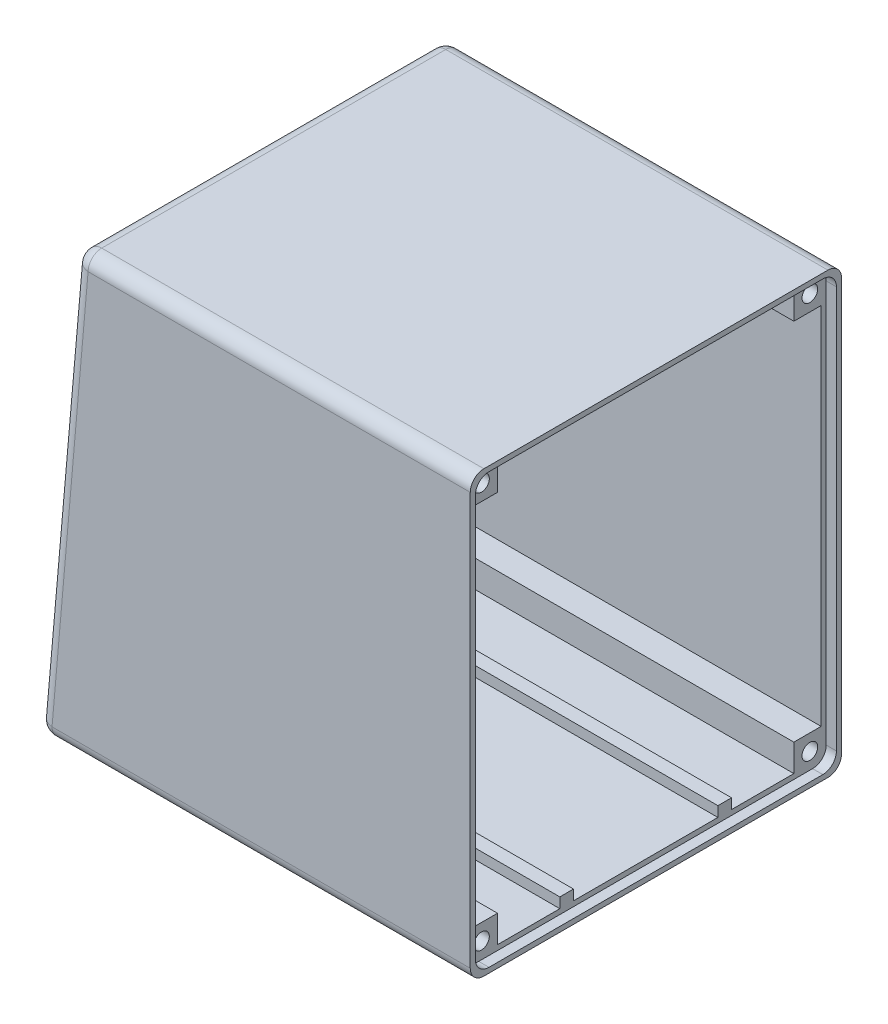
SolidWorks part; units mm, degrees
material "POM 乙缩醛共聚物"
ref_plane "前视基准面" through (0, 0, 0) normal (0, 0, 1) x (1, 0, 0)
ref_plane "上视基准面" through (0, 0, 0) normal (0, 1, 0) x (1, 0, 0)
ref_plane "右视基准面" through (0, 0, 0) normal (1, 0, 0) x (0, 0, -1)
sketch "草图1" plane through (0, 0, 0) normal (0, 0, 1) x (1, 0, 0)
  line L0 (0, 0) -> (62, 0)
  line L1 (0, 0) -> (5.5118, 63)
  line L2 (5.5118, 63) -> (62, 63)
  line L3 (62, 0) -> (62, 63)
  dimension "D1" = 85
  dimension "D2" = 62
  dimension "D3" = 63
extrude "拉伸-薄壁1" add sketch "草图1" along normal mid plane 53 thin thin type mid plane wall 1.5
sketch "草图2" plane through (0, 0, -26.5) normal (0, 0, -1) x (-1, 0, 0)
  line L4 (0.8185, -0.75) -> (-4.8245, 63.75)
  line L5 (-4.8245, 63.75) -> (-62.75, 63.75)
  line L6 (-62.75, 63.75) -> (-62.75, -0.75)
  line L7 (-62.75, -0.75) -> (0.8185, -0.75)
  line L8 (0.8185, -0.75) -> (-4.8245, 63.75)
  line L9 (-4.8245, 63.75) -> (-62.75, 63.75)
  line L10 (-62.75, 63.75) -> (-62.75, -0.75)
  line L11 (-62.75, -0.75) -> (0.8185, -0.75)
  dimension "D1" = 0
extrude "凸台-拉伸1" add sketch "草图2" along normal mid plane 1.5
sketch "草图3" plane through (0, 0, 26.5) normal (0, 0, 1) x (1, 0, 0)
  line L4 (4.8245, 63.75) -> (-0.8185, -0.75)
  line L5 (-0.8185, -0.75) -> (62.75, -0.75)
  line L6 (62.75, -0.75) -> (62.75, 63.75)
  line L7 (62.75, 63.75) -> (4.8245, 63.75)
  line L8 (4.8245, 63.75) -> (-0.8185, -0.75)
  line L9 (-0.8185, -0.75) -> (62.75, -0.75)
  line L10 (62.75, -0.75) -> (62.75, 63.75)
  line L11 (62.75, 63.75) -> (4.8245, 63.75)
  dimension "D1" = 0
extrude "凸台-拉伸2" add sketch "草图3" along normal mid plane 1.5
sketch "草图4" plane through (62.75, 0, 0) normal (1, 0, 0) x (0, 0, -1)
  line L0 (-25.75, 62.25) -> (25.75, 62.25)
  line L1 (25.75, 62.25) -> (25.75, 0.75)
  line L2 (25.75, 0.75) -> (-25.75, 0.75)
  line L3 (-25.75, 0.75) -> (-25.75, 62.25)
  line L4 (-27.25, 63.75) -> (27.25, 63.75) construction
  line L5 (-27.25, -0.75) -> (-27.25, 63.75) construction
  line L6 (27.25, 63.75) -> (27.25, -0.75) construction
  line L7 (-27.25, -0.75) -> (27.25, -0.75) construction
  dimension "D1" = 1.5
  dimension "D2" = 1.5
  dimension "D3" = 1.5
  dimension "D4" = 1.5
extrude "切除-拉伸1" cut sketch "草图4" against normal up to next
sketch "草图5" plane through (0, -0.75, 0) normal (0, -1, 0) x (1, 0, 0)
  line L0 (-0.8185, 0) -> (62.75, 0) construction
  line L1 (-0.8185, 27.25) -> (-0.8185, -27.25) construction
  line L2 (62.75, 27.25) -> (62.75, -27.25) construction
  line L3 (30.9658, 27.25) -> (30.9658, -27.25) construction
  line L4 (-0.8185, 27.25) -> (62.75, 27.25) construction
  line L5 (62.75, -27.25) -> (-0.8185, -27.25) construction
  circle A0 centre (6.5619, 14.1382) radius 4
  circle A1 centre (55.3696, 14.1382) radius 4
  circle A2 centre (55.3696, -14.1382) radius 4
  circle A3 centre (6.5619, -14.1382) radius 4
  dimension "D1" = 8
extrude "凸台-拉伸3" add sketch "草图5" along normal blind 0.5 contours A3 | A1 | A2 | A0 region at (55.3696, -0.75, 14.1382) region at (55.3696, -0.75, -14.1382) region at (6.5619, -0.75, -14.1382)
fillet "圆角2" radius 2 5 edges at (33.7873, 63.75, 27.25) (2.003, 31.5, 27.25) (33.7873, 63.75, -27.25) (2.003, 31.5, -27.25) (4.8245, 63.75, 0)
ref_plane "基准面1" through (62.75, 0, 0) normal (1, 0, 0) x (0, 0, -1)
sketch "草图12" plane through (62.75, 0, 0) normal (1, 0, 0) x (0, 0, -1)
  line L1 (-25.75, 62.25) -> (-21.75, 62.25)
  line L2 (-25.75, 62.25) -> (-25.75, 58.25)
  line L3 (-25.75, 58.25) -> (-21.75, 58.25)
  line L4 (-21.75, 62.25) -> (-21.75, 58.25)
  line L8 (0, 62.25) -> (0, 0.75) construction
  line L9 (-25.75, 62.25) -> (25.75, 62.25) construction
  line L10 (-25.75, 0.75) -> (25.75, 0.75) construction
  line L11 (-25.75, 31.5) -> (25.75, 31.5) construction
  line L12 (-25.75, 0.75) -> (-25.75, 62.25) construction
  line L13 (25.75, 62.25) -> (25.75, 0.75) construction
  line L14 (25.75, 58.25) -> (21.75, 58.25)
  line L15 (21.75, 62.25) -> (21.75, 58.25)
  line L16 (25.75, 62.25) -> (21.75, 62.25)
  line L17 (25.75, 62.25) -> (25.75, 58.25)
  line L18 (25.75, 0.75) -> (25.75, 4.75)
  line L19 (25.75, 0.75) -> (21.75, 0.75)
  line L20 (21.75, 0.75) -> (21.75, 4.75)
  line L21 (25.75, 4.75) -> (21.75, 4.75)
  line L22 (-25.75, 4.75) -> (-21.75, 4.75)
  line L23 (-21.75, 0.75) -> (-21.75, 4.75)
  line L24 (-25.75, 0.75) -> (-21.75, 0.75)
  line L25 (-25.75, 0.75) -> (-25.75, 4.75)
  dimension "D1" = 4
  dimension "D2" = 4
extrude "凸台-拉伸4" add sketch "草图12" against normal up to next
sketch "草图13" plane through (62.75, 0, 0) normal (1, 0, 0) x (0, 0, -1)
  line L0 (-25.25, 63.75) -> (25.25, 63.75) construction
  line L1 (0, 63.75) -> (0, 0) construction
  line L2 (-27.25, -0.75) -> (-27.25, 61.75) construction
  line L7 (-27.25, -0.75) -> (27.25, -0.75) construction
  circle A0 centre (-24.1, 60.6) radius 1.15
  circle A1 centre (24.1, 60.6) radius 1.15
  circle A2 centre (-24.1, 2.4) radius 1.15
  circle A3 centre (24.1, 2.4) radius 1.15
  dimension "D1" = 2.3
  dimension "D2" = 3.15
  dimension "D4" = 3.15
  dimension "D6" = 2.3
  dimension "D3" = 3.15
  dimension "D5" = 3.15
extrude "切除-拉伸3" cut sketch "草图13" against normal blind 8
sketch "草图15" plane through (-0.7471, 0.0654, 0) normal (-0.9962, 0.0872, 0) x (0, 0, 1)
  line L1 (18.7329, 59.1814) -> (-18.6323, 59.1814)
  line L2 (18.7329, 59.1814) -> (18.7329, 9.6024)
  line L3 (18.7329, 9.6024) -> (-18.6323, 9.6024)
  line L4 (-18.6323, 59.1814) -> (-18.6323, 9.6024)
extrude "切除-拉伸4" cut sketch "草图15" against normal through all
fillet "圆角4" radius 1 4 edges at (0.0898, 9.6312, 0.0503) (2.2503, 34.3264, 18.7329) (4.4109, 59.0216, 0.0503) (2.2503, 34.3264, -18.6323)
sketch "草图18" plane through (62.75, 0, 0) normal (1, 0, 0) x (0, 0, -1)
  line L0 (-27.25, -0.75) -> (-27.25, 61.75) construction
  line L1 (-26.5, 63) -> (26.5, 63)
  line L2 (-26.5, 63) -> (-26.5, 0)
  line L3 (-26.5, 0) -> (26.5, 0)
  line L4 (26.5, 63) -> (26.5, 0)
  line L5 (27.25, 61.75) -> (27.25, -0.75) construction
  line L6 (-25.25, 63.75) -> (25.25, 63.75) construction
  line L7 (-27.25, -0.75) -> (27.25, -0.75) construction
  dimension "D1" = 0.75
  dimension "D2" = 0.75
  dimension "D3" = 0.75
  dimension "D4" = 0.75
extrude "切除-拉伸5" cut sketch "草图18" against normal blind 1.5
fillet "圆角5" radius 2 4 edges at (62, 63, -26.5) (62, 63, 26.5) (62, 0, -26.5) (62, 0, 26.5)
fillet "圆角6" radius 2 5 edges at (31.9696, -0.75, 27.25) (-0.2305, -0.75, 26.6642) (31.9696, -0.75, -27.25) (-0.2305, -0.75, -26.6642) (-0.8185, -0.75, 0)
sketch "草图22" plane through (0, -0.75, 0) normal (0, -1, 0) x (1, 0, 0)
  line L0 (61.25, 25.25) -> (61.25, -25.25) construction
  line L3 (62.75, 25.25) -> (1.3641, 25.25) construction
  line L4 (1.3641, -25.25) -> (62.75, -25.25) construction
  line L5 (62.75, 25.25) -> (62.75, -25.25) construction
  line L7 (1.3641, 0) -> (61.25, 0) construction
  line L8 (1.3641, 25.25) -> (1.3641, -25.25) construction
  line L9 (61.25, 10.6) -> (10.25, 10.6)
  line L10 (10.25, 10.6) -> (10.25, -10.6)
  line L11 (10.25, -10.6) -> (61.25, -10.6)
  dimension "D1" = 1.5
  dimension "D2" = 51
  dimension "D3" = 21.2
  dimension "D4" = 10.6
extrude "拉伸-薄壁4" add sketch "草图22" against normal blind 3 thin thin type one direction wall 2
